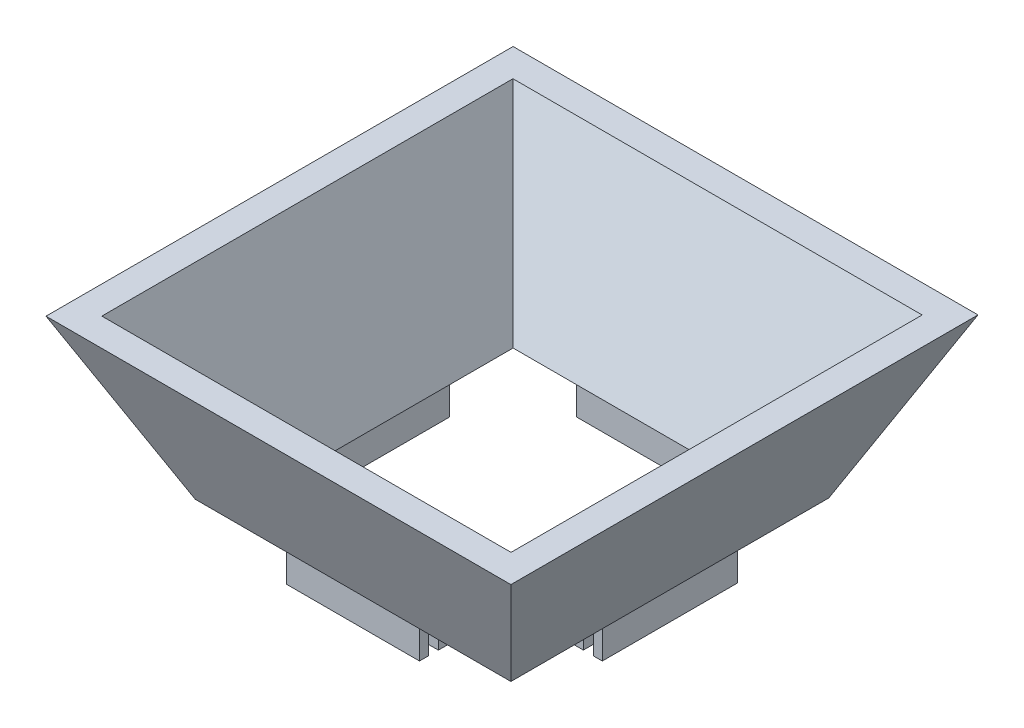
SolidWorks part; units mm, degrees
ref_plane "Front Plane" through (0, 0, 0) normal (0, 0, 1) x (1, 0, 0)
ref_plane "Top Plane" through (0, 0, 0) normal (0, 1, 0) x (1, 0, 0)
ref_plane "Right Plane" through (0, 0, 0) normal (1, 0, 0) x (0, 0, -1)
sketch "Sketch1" plane through (0, 0, 0) normal (0, 1, 0) x (1, 0, 0)
  line L0 (94.57, 95.37) -> (101.3, 95.37) construction
  line L1 (-94.57, -95.37) -> (94.57, -95.37)
  line L2 (-94.57, -95.37) -> (-94.57, 95.37)
  line L3 (-94.57, 95.37) -> (94.57, 95.37)
  line L4 (94.57, -95.37) -> (94.57, 95.37)
  line L5 (-94.57, -95.37) -> (94.57, 95.37) construction
  line L6 (-94.57, 95.37) -> (94.57, -95.37) construction
  line L7 (-101.3, -102.1) -> (101.3, -102.1)
  line L8 (-101.3, -102.1) -> (-101.3, 102.1)
  line L9 (-101.3, 102.1) -> (101.3, 102.1)
  line L10 (101.3, -102.1) -> (101.3, 102.1)
  line L11 (-101.3, -102.1) -> (101.3, 102.1) construction
  line L12 (-101.3, 102.1) -> (101.3, -102.1) construction
  line L13 (-88.41, -89.1579) -> (88.41, -89.1579)
  line L14 (-88.41, -89.1579) -> (-88.41, 89.1579)
  line L15 (-88.41, 89.1579) -> (88.41, 89.1579)
  line L16 (88.41, -89.1579) -> (88.41, 89.1579)
  line L17 (-88.41, -89.1579) -> (88.41, 89.1579) construction
  line L18 (-88.41, 89.1579) -> (88.41, -89.1579) construction
  line L19 (-107.46, -108.2079) -> (107.46, -108.2079)
  line L20 (-107.46, -108.2079) -> (-107.46, 108.2079)
  line L21 (-107.46, 108.2079) -> (107.46, 108.2079)
  line L22 (107.46, -108.2079) -> (107.46, 108.2079)
  line L23 (-107.46, -108.2079) -> (107.46, 108.2079) construction
  line L24 (-107.46, 108.2079) -> (107.46, -108.2079) construction
  point P0 (0, 0)
  point P6 (0, 0)
  point P11 (0, 0)
  point P16 (0, 0)
  point P21 (97.935, 95.37)
  dimension "D1" = 189.14
  dimension "D2" = 190.74
  dimension "D3" = 6.73
  dimension "D4" = 6.73
  dimension "D5" = 19.05
  dimension "D6" = 19.05
  dimension "D7" = 9.525
extrude "Boss-Extrude2" add sketch "Sketch1" along normal blind 19.05 contours L1 L4 L3 L2 L16 L13 L14 L15 | L19 L22 L21 L20 L10 L7 L8 L9 region at (-91.8838, 0, 0) region at (-104.41, 0, 0)
ref_plane "Plane1" through (0, 127, 0) normal (0, 1, 0) x (1, 0, 0)
sketch "Sketch2" plane through (0, 127, 0) normal (0, 1, 0) x (1, 0, 0)
  line L9 (-158.26, -159.0079) -> (158.26, -159.0079)
  line L10 (-158.26, -159.0079) -> (-158.26, 159.0079)
  line L11 (-158.26, 159.0079) -> (158.26, 159.0079)
  line L12 (158.26, -159.0079) -> (158.26, 159.0079)
  line L13 (-158.26, -159.0079) -> (158.26, 159.0079) construction
  line L14 (-158.26, 159.0079) -> (158.26, -159.0079) construction
  point P0 (0, 0)
  point P1 (0, 0)
  point P10 (0, 0)
  dimension "D1" = 316.52
  dimension "D4" = 318.0158
sketch "Sketch4" plane through (0, 19.05, 0) normal (0, 1, 0) x (1, 0, 0)
  line L0 (-88.41, -89.1579) -> (88.41, -89.1579) construction
  line L5 (-88.41, -89.1579) -> (88.41, 89.1579) construction
  line L6 (-88.41, 89.1579) -> (88.41, -89.1579) construction
  line L7 (-107.46, 108.2079) -> (107.46, 108.2079) construction
  line L8 (-107.46, 108.2079) -> (107.46, 108.2079)
  line L9 (-107.46, 108.2079) -> (-107.46, -108.2079)
  line L10 (-107.46, -108.2079) -> (107.46, -108.2079)
  line L11 (107.46, 108.2079) -> (107.46, -108.2079)
  line L12 (-107.46, 108.2079) -> (107.46, -108.2079) construction
  line L13 (-107.46, -108.2079) -> (107.46, 108.2079) construction
  line L14 (-107.46, -108.2079) -> (-107.46, 108.2079) construction
  point P0 (0, 0)
  point P6 (-107.46, 108.2079)
  point P11 (0, 0)
sketch "Sketch5" plane through (0, 19.05, 0) normal (0, 1, 0) x (1, 0, 0)
  line L1 (-88.41, 89.1579) -> (88.41, 89.1579)
  line L2 (-88.41, 89.1579) -> (-88.41, -89.1579)
  line L3 (-88.41, -89.1579) -> (88.41, -89.1579)
  line L4 (88.41, 89.1579) -> (88.41, -89.1579)
sketch "Sketch6" plane through (0, 127, 0) normal (0, 1, 0) x (1, 0, 0)
  line L0 (-158.26, -159.0079) -> (158.26, 159.0079) construction
  line L1 (-139.2996, -139.9579) -> (139.2996, -139.9579)
  line L2 (-139.2996, -139.9579) -> (-139.2996, 139.9579)
  line L3 (-139.2996, 139.9579) -> (139.2996, 139.9579)
  line L4 (139.2996, -139.9579) -> (139.2996, 139.9579)
  line L5 (-139.2996, -139.9579) -> (139.2996, 139.9579) construction
  line L6 (-139.2996, 139.9579) -> (139.2996, -139.9579) construction
  line L7 (-158.26, 159.0079) -> (158.26, 159.0079) construction
  point P0 (0, 0)
  dimension "D1" = 19.05
loft "Loft1" add profiles "Sketch2", "Sketch4" connector at (-158.26, 127, 159.0079) connector at (-107.46, 19.05, 108.2079)
loft "Cut-Loft1" cut profiles "Sketch6", "Sketch5" connector at (-139.2996, 127, 139.9579) connector at (-88.41, 19.05, 89.1579)
sketch "Sketch7" plane through (0, 19.05, 0) normal (0, -1, 0) x (1, 0, 0)
  line L0 (88.41, 89.1579) -> (88.41, -89.1579) construction
  line L1 (-271.29, 272.0379) -> (-45.23, 272.0379)
  line L2 (-271.29, 272.0379) -> (-271.29, 45.9779)
  line L3 (-271.29, 45.9779) -> (-45.23, 45.9779)
  line L4 (-45.23, 272.0379) -> (-45.23, 45.9779)
  line L5 (-271.29, 272.0379) -> (-45.23, 45.9779) construction
  line L6 (-271.29, 45.9779) -> (-45.23, 272.0379) construction
  line L7 (271.29, 272.0379) -> (45.23, 272.0379)
  line L8 (271.29, 272.0379) -> (271.29, 45.9779)
  line L9 (271.29, 45.9779) -> (45.23, 45.9779)
  line L10 (45.23, 272.0379) -> (45.23, 45.9779)
  line L11 (271.29, 272.0379) -> (45.23, 45.9779) construction
  line L12 (271.29, 45.9779) -> (45.23, 272.0379) construction
  line L13 (-271.29, -272.0379) -> (-45.23, -272.0379)
  line L14 (-271.29, -272.0379) -> (-271.29, -45.9779)
  line L15 (-271.29, -45.9779) -> (-45.23, -45.9779)
  line L16 (-45.23, -272.0379) -> (-45.23, -45.9779)
  line L17 (-271.29, -272.0379) -> (-45.23, -45.9779) construction
  line L18 (-271.29, -45.9779) -> (-45.23, -272.0379) construction
  line L19 (45.23, -272.0379) -> (271.29, -272.0379)
  line L20 (45.23, -272.0379) -> (45.23, -45.9779)
  line L21 (45.23, -45.9779) -> (271.29, -45.9779)
  line L22 (271.29, -272.0379) -> (271.29, -45.9779)
  line L23 (45.23, -272.0379) -> (271.29, -45.9779) construction
  line L24 (45.23, -45.9779) -> (271.29, -272.0379) construction
  line L25 (-88.41, 89.1579) -> (88.41, 89.1579) construction
  line L26 (-88.41, -89.1579) -> (88.41, -89.1579) construction
  line L27 (-88.41, 89.1579) -> (-88.41, -89.1579) construction
  point P0 (-158.26, 159.0079)
  point P6 (158.26, 159.0079)
  point P12 (-158.26, -159.0079)
  point P18 (158.26, -159.0079)
  dimension "D1" = 43.18
  dimension "D2" = 43.18
  dimension "D3" = 43.18
  dimension "D4" = 43.18
  dimension "D5" = 43.18
  dimension "D6" = 43.18
  dimension "D7" = 43.18
  dimension "D8" = 43.18
extrude "Cut-Extrude1" cut sketch "Sketch7" along normal blind 255
